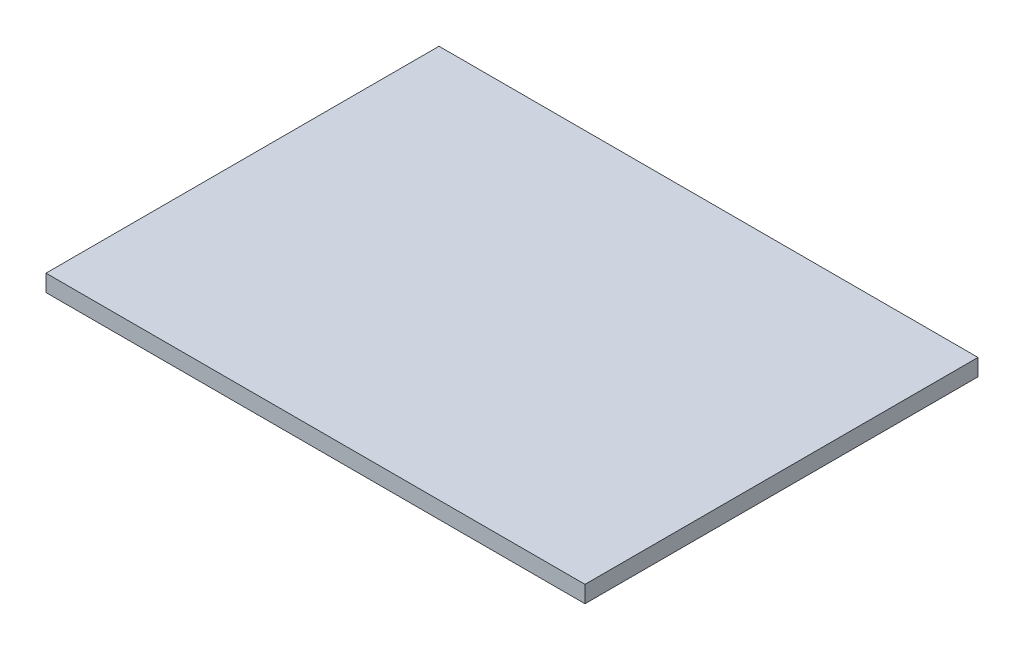
SolidWorks part; units mm, degrees
ref_plane "Front Plane" through (0, 0, 0) normal (0, 0, 1) x (1, 0, 0)
ref_plane "Top Plane" through (0, 0, 0) normal (0, 1, 0) x (1, 0, 0)
ref_plane "Right Plane" through (0, 0, 0) normal (1, 0, 0) x (0, 0, -1)
sketch "Sketch1" plane through (0, 0, 0) normal (0, 1, 0) x (1, 0, 0)
  line L0 (5.08, 5.08) -> (238.76, 5.08)
  line L1 (0, 0) -> (243.84, 0)
  line L2 (0, 0) -> (0, 177.8)
  line L3 (0, 177.8) -> (243.84, 177.8)
  line L4 (243.84, 0) -> (243.84, 177.8)
  line L5 (238.76, 5.08) -> (238.76, 172.72)
  line L6 (5.08, 172.72) -> (238.76, 172.72)
  line L7 (5.08, 5.08) -> (5.08, 172.72)
  dimension "D1" = 177.8
  dimension "D2" = 243.84
  dimension "D3" = 5.08
extrude "Boss-Extrude7" add sketch "Sketch1" along normal blind 7.62
sketch "Sketch6" plane through (0, 7.62, 0) normal (0, 1, 0) x (1, 0, 0)
  line L0 (5.08, 172.72) -> (5.08, 5.08)
  line L1 (5.08, 5.08) -> (238.76, 5.08)
  line L2 (238.76, 5.08) -> (238.76, 172.72)
  line L3 (238.76, 172.72) -> (5.08, 172.72)
extrude "Boss-Extrude8" add sketch "Sketch6" against normal blind 7.62
sketch "Sketch7" plane through (0, 7.62, 0) normal (0, 1, 0) x (1, 0, 0)
  line L0 (0, 0) -> (243.84, 0) construction
  line L1 (0, 177.8) -> (0, 0) construction
  line L2 (243.84, 0) -> (243.84, 177.8) construction
  line L3 (196.37, 1.27) -> (178.2581, 1.27)
  line L4 (47.47, 1.27) -> (47.47, 63.07)
  line L6 (196.37, 63.07) -> (196.37, 1.27)
  line L8 (47.47, 32.17) -> (0, 32.17) construction
  line L9 (196.37, 32.17) -> (243.84, 32.17) construction
  line L11 (168.0981, 0) -> (178.2581, 0)
  line L12 (178.2581, 0) -> (178.2581, 1.27)
  line L14 (157.9954, 1.27) -> (47.47, 1.27)
  line L15 (157.9954, 1.27) -> (168.0981, 1.27)
  line L16 (168.0981, 1.27) -> (168.0981, 0)
  line L18 (183.67, 64.34) -> (145.57, 64.34)
  line L20 (196.37, 63.07) -> (183.67, 63.07)
  line L21 (145.57, 63.07) -> (47.47, 63.07)
  line L22 (183.67, 63.07) -> (183.67, 64.34)
  line L23 (145.57, 63.07) -> (145.57, 64.34)
  dimension "D1" = 1.27
  dimension "D2" = 148.9
  dimension "D3" = 61.8
  dimension "D4" = 10.16
  dimension "D5" = 38.1
  dimension "D6" = 12.7
  dimension "D7" = 1.27
